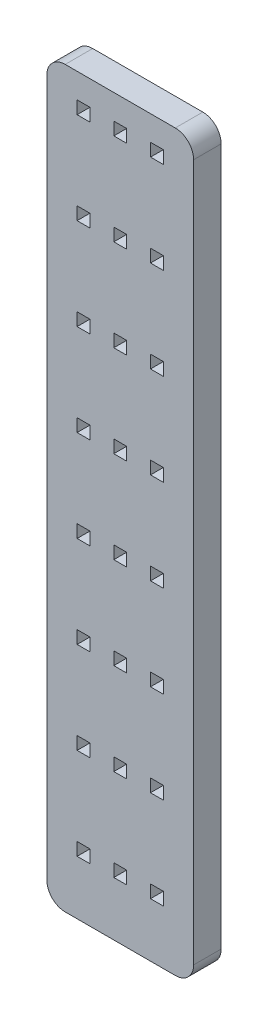
SolidWorks part; units mm, degrees
ref_plane "Front Plane" through (0, 0, 0) normal (0, 0, 1) x (1, 0, 0)
ref_plane "Top Plane" through (0, 0, 0) normal (0, 1, 0) x (1, 0, 0)
ref_plane "Right Plane" through (0, 0, 0) normal (1, 0, 0) x (0, 0, -1)
sketch "Sketch1" plane through (0, 0, 0) normal (0, 0, 1) x (1, 0, 0)
  line L1 (4, -2.5) -> (-4, -2.5)
  line L2 (4, -2.5) -> (4, 2.5)
  line L3 (4, 2.5) -> (-4, 2.5)
  line L4 (-4, -2.5) -> (-4, 2.5)
  line L5 (4, -2.5) -> (-4, 2.5) construction
  line L6 (4, 2.5) -> (-4, -2.5) construction
  point P0 (0, 0)
  dimension "D1" = 5
  dimension "D2" = 8
extrude "Boss-Extrude1" add sketch "Sketch1" along normal blind 1.5
sketch "Sketch2" plane through (0, 0, 1.5) normal (0, 0, 1) x (1, 0, 0)
  line L0 (-4, 0.8) -> (4, 0.8) construction
  line L1 (-4, 2.5) -> (-4, -2.5) construction
  line L2 (4, -2.5) -> (4, 2.5) construction
  line L3 (-4, -2.5) -> (4, -2.5) construction
  line L5 (-2.35, 0.45) -> (-1.65, 0.45)
  line L6 (-2.35, 0.45) -> (-2.35, 1.15)
  line L7 (-2.35, 1.15) -> (-1.65, 1.15)
  line L8 (-1.65, 0.45) -> (-1.65, 1.15)
  line L9 (-2.35, 0.45) -> (-1.65, 1.15) construction
  line L10 (-2.35, 1.15) -> (-1.65, 0.45) construction
  line L11 (-0.35, 0.45) -> (0.35, 0.45)
  line L12 (-0.35, 0.45) -> (-0.35, 1.15)
  line L13 (-0.35, 1.15) -> (0.35, 1.15)
  line L14 (0.35, 0.45) -> (0.35, 1.15)
  line L15 (-0.35, 0.45) -> (0.35, 1.15) construction
  line L16 (-0.35, 1.15) -> (0.35, 0.45) construction
  line L17 (1.65, 0.45) -> (2.35, 0.45)
  line L18 (1.65, 0.45) -> (1.65, 1.15)
  line L19 (1.65, 1.15) -> (2.35, 1.15)
  line L20 (2.35, 0.45) -> (2.35, 1.15)
  line L21 (1.65, 0.45) -> (2.35, 1.15) construction
  line L22 (1.65, 1.15) -> (2.35, 0.45) construction
  point P8 (-2, 0.8)
  point P13 (0, 0.8)
  point P18 (2, 0.8)
  dimension "D1" = 3.3
  dimension "D2" = 0.7
  dimension "D3" = 2
  dimension "D4" = 2
extrude "Cut-Extrude1" cut sketch "Sketch2" against normal through all
pattern_linear "LPattern1" count 8 spacing 5 along (0, -1, 0) of bodies 102
combine bodies "Combine1" operation type add bodies to combine 102 103 104 105 106 107 108 109
fillet "Fillet1" radius 1 4 edges at (-4, -37.5, 0.75) (4, -37.5, 0.75) (4, 2.5, 0.75) (-4, 2.5, 0.75)
